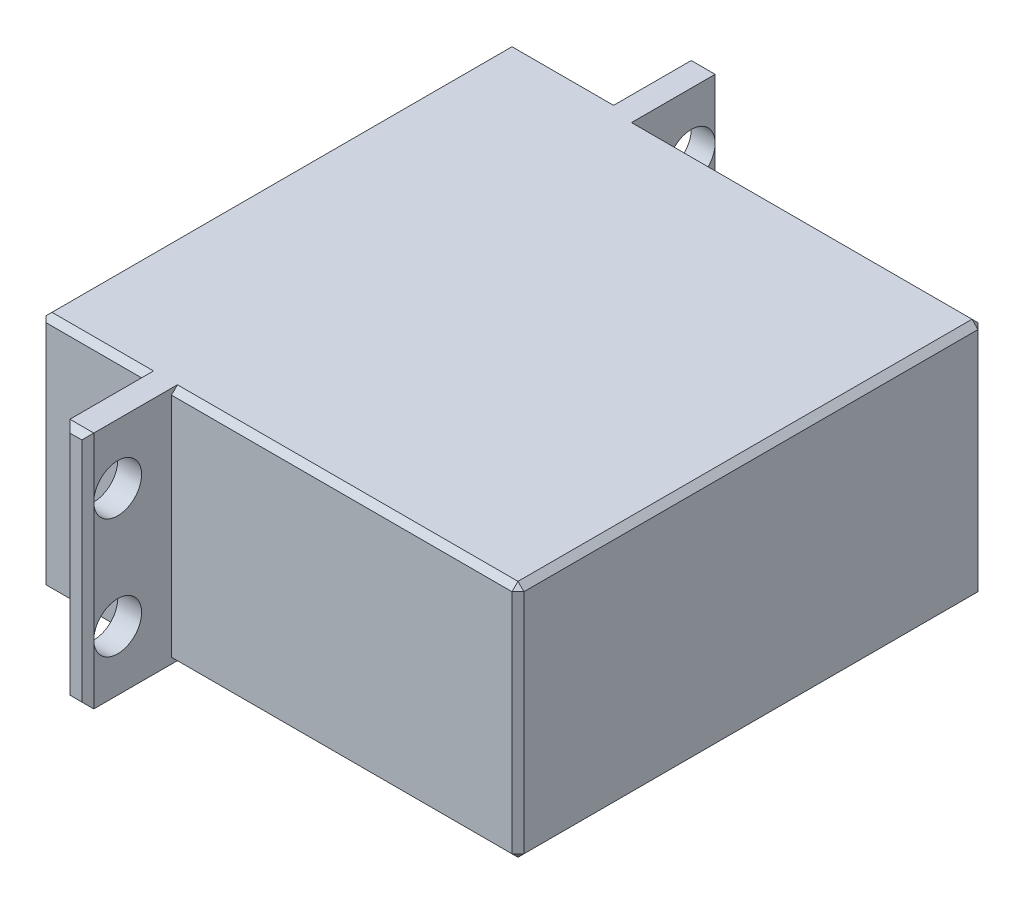
SolidWorks part; units mm, degrees
ref_plane "前视基准面" through (0, 0, 0) normal (0, 0, 1) x (1, 0, 0)
ref_plane "上视基准面" through (0, 0, 0) normal (0, 1, 0) x (1, 0, 0)
ref_plane "右视基准面" through (0, 0, 0) normal (1, 0, 0) x (0, 0, -1)
sketch "草图1" plane through (0, 0, 0) normal (0, 1, 0) x (1, 0, 0)
  line L1 (0, 0) -> (-40, 0)
  line L2 (0, 0) -> (0, -39)
  line L3 (0, -39) -> (-40, -39)
  line L4 (-40, 0) -> (-40, -39)
extrude "凸台-拉伸1" add sketch "草图1" along normal blind 20
sketch "草图4" plane through (-40, 0, 0) normal (-1, 0, 0) x (0, 0, 1)
  circle A0 centre (10, 10) radius 3
extrude "凸台-拉伸2" add sketch "草图4" along normal blind 1
sketch "草图5" plane through (-41, 0, 0) normal (-1, 0, 0) x (0, 0, 1)
  circle A0 centre (10, 10) radius 2.5
extrude "凸台-拉伸3" add sketch "草图5" along normal blind 0.5
sketch "草图6" plane through (-41.5, 0, 0) normal (-1, 0, 0) x (0, 0, 1)
  circle A0 centre (10, 10) radius 1.5
extrude "凸台-拉伸4" add sketch "草图6" along normal blind 3.5
sketch "草图8" plane through (0, 0, 0) normal (0, 0, -1) x (-1, 0, 0)
  line L1 (0, 20) -> (40, 20) construction
  line L2 (31, 20) -> (31, 0)
  line L3 (0, 0) -> (40, 0) construction
  line L4 (31, 0) -> (29, 0)
  line L5 (29, 0) -> (29, 20)
  line L6 (29, 20) -> (31, 20)
extrude "凸台-拉伸5" add sketch "草图8" along normal blind 7
sketch "草图9" plane through (-31, 0, 0) normal (-1, 0, 0) x (0, 0, 1)
  circle A0 centre (-4.5, 5) radius 2
  circle A1 centre (-4.5, 15) radius 2
extrude "切除-拉伸1" cut sketch "草图9" against normal blind 3
ref_plane "基准面4" through (0, 0, 19.5) normal (0, 0, -1) x (-1, 0, 0)
mirror "镜向5" about plane through (0, 0, 19.5) normal (0, 0, -1) of "切除-拉伸1", "凸台-拉伸5"
chamfer "倒角2" distance 0.5 angle 45 4 edges at (-40, 20, 19.5) (-40, 10, 39) (-40, 0, 19.5) (-40, 10, 0)
sketch "草图16" plane through (-45, 0, 0) normal (-1, 0, 0) x (0, 0, 1)
  circle A0 centre (10, 10) radius 0.75
extrude "切除-拉伸2" cut sketch "草图16" against normal blind 10
chamfer "倒角4" distance 0.5 angle 45 19 edges at (-35.25, 0, 39) (-30, 20, -7) (-31, 10, -7) (-30, 0, -7) (-29, 10, -7) (-35.25, 0, 0) (0, 10, 39) (-14.5, 20, 39) (0, 20, 19.5) (-14.5, 0, 39) (0, 0, 19.5) (-14.5, 0, 0) (0, 10, 0) (-14.5, 20, 0) (-30, 0, 46) (-29, 10, 46) (-31, 10, 46) (-30, 20, 46) (-35.25, 20, 39)
